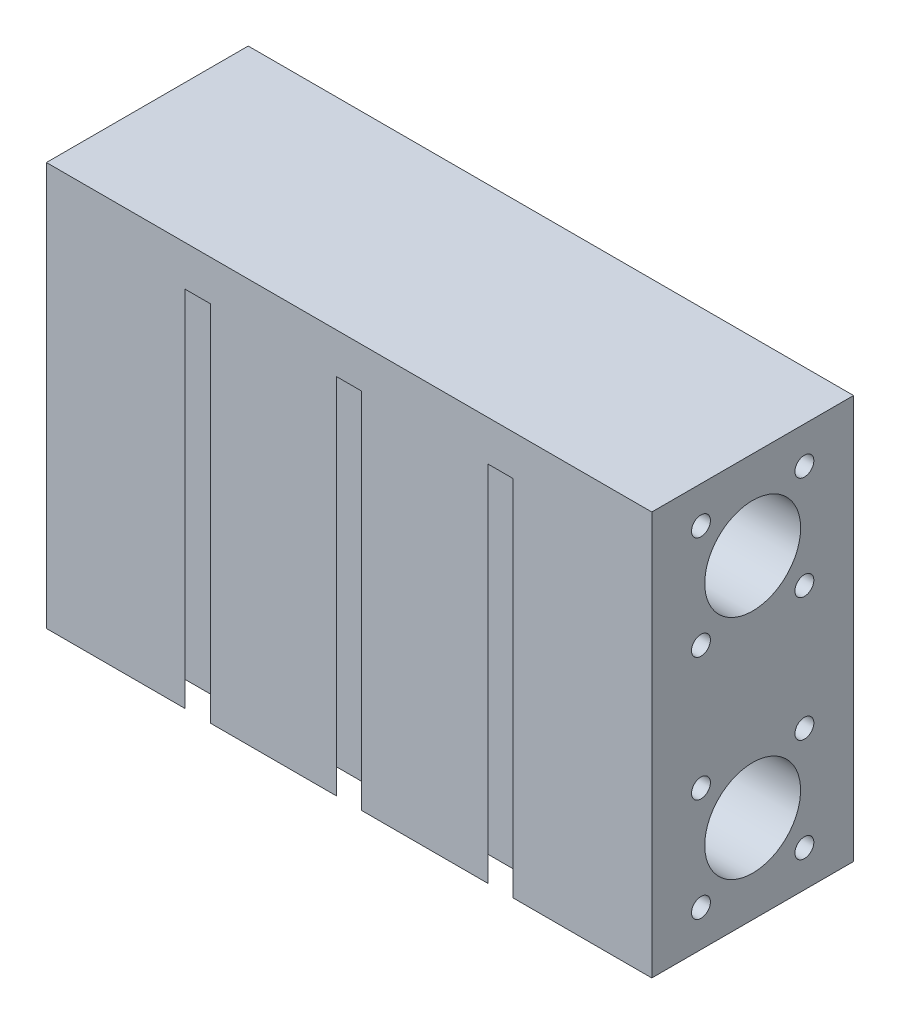
SolidWorks part; units mm, degrees
ref_plane "Front Plane" through (0, 0, 0) normal (0, 0, 1) x (1, 0, 0)
ref_plane "Top Plane" through (0, 0, 0) normal (0, 1, 0) x (1, 0, 0)
ref_plane "Right Plane" through (0, 0, 0) normal (1, 0, 0) x (0, 0, -1)
sketch "Sketch1" plane through (0, 0, 0) normal (0, 0, 1) x (1, 0, 0)
  line L1 (0, 0) -> (120, 0)
  line L2 (0, 0) -> (0, 80)
  line L3 (0, 80) -> (120, 80)
  line L4 (120, 0) -> (120, 80)
  dimension "D1" = 80
  dimension "D2" = 120
extrude "Boss-Extrude1" add sketch "Sketch1" along normal blind 40 contours L3 L4 L1 L2
sketch "Sketch2" plane through (0, 0, 0) normal (-1, 0, 0) x (0, 0, 1)
  line L0 (20, 80) -> (20, 0) construction
  line L1 (40, 80) -> (0, 80) construction
  line L2 (40, 0) -> (0, 0) construction
  line L3 (40, 40) -> (0, 40) construction
  line L4 (40, 0) -> (40, 80) construction
  line L5 (0, 0) -> (0, 80) construction
  line L6 (0, 62.5) -> (40, 62.5) construction
  line L7 (0, 17.5) -> (40, 17.5) construction
  circle A1 centre (30.25, 72.75) radius 1.85
  circle A2 centre (9.75, 72.75) radius 1.85
  circle A3 centre (30.25, 52.25) radius 1.85
  circle A4 centre (9.75, 52.25) radius 1.85
  circle A5 centre (9.75, 27.75) radius 1.85
  circle A6 centre (30.25, 27.75) radius 1.85
  circle A7 centre (30.25, 7.25) radius 1.85
  circle A9 centre (9.75, 7.25) radius 1.85
  dimension "D4" = 3.7
  dimension "D1" = 22.5
  dimension "D2" = 9.75
  dimension "D3" = 7.25
extrude "linear-bearing-screw-cuts" cut sketch "Sketch2" against normal blind 14
sketch "Sketch3" plane through (0, 0, 0) normal (-1, 0, 0) x (0, 0, 1)
  line L0 (20, 80) -> (20, 0) construction
  line L1 (40, 80) -> (0, 80) construction
  line L2 (40, 0) -> (0, 0) construction
  line L3 (0, 40) -> (40, 40) construction
  line L4 (0, 0) -> (0, 80) construction
  line L5 (40, 0) -> (40, 80) construction
  line L6 (0, 62.5) -> (40, 62.5) construction
  line L7 (0, 17.5) -> (40, 17.5) construction
  circle A0 centre (20, 62.5) radius 9.5
  circle A2 centre (20, 17.5) radius 9.5
  dimension "D2" = 19
  dimension "D1" = 45
extrude "linear-bearings-hole" cut sketch "Sketch3" against normal blind 55
sketch "Sketch4" plane through (120, 0, 0) normal (1, 0, 0) x (0, 0, -1)
  line L0 (-20, 80) -> (-20, 0) construction
  line L1 (-40, 80) -> (0, 80) construction
  line L2 (-40, 0) -> (0, 0) construction
  line L3 (-40, 40) -> (0, 40) construction
  line L4 (-40, 0) -> (-40, 80) construction
  line L5 (0, 0) -> (0, 80) construction
  line L6 (-40, 62.5) -> (0, 62.5) construction
  line L7 (-40, 17.5) -> (0, 17.5) construction
  circle A0 centre (-9.75, 72.75) radius 1.875
  circle A1 centre (-30.25, 72.75) radius 1.875
  circle A2 centre (-9.75, 52.25) radius 1.875
  circle A3 centre (-30.25, 52.25) radius 1.875
  circle A4 centre (-30.25, 27.75) radius 1.875
  circle A5 centre (-9.75, 27.75) radius 1.875
  circle A6 centre (-9.75, 7.25) radius 1.875
  circle A7 centre (-30.25, 7.25) radius 1.875
  dimension "D2" = 3.75
  dimension "D1" = 45
  dimension "D3" = 7.25
  dimension "D4" = 9.75
extrude "linear-bearing-screw-cuts2" cut sketch "Sketch4" against normal blind 14
sketch "Sketch5" plane through (120, 0, 0) normal (1, 0, 0) x (0, 0, -1)
  line L0 (-20, 80) -> (-20, 0) construction
  line L1 (-40, 80) -> (0, 80) construction
  line L2 (-40, 0) -> (0, 0) construction
  line L3 (0, 40) -> (-40, 40) construction
  line L4 (0, 0) -> (0, 80) construction
  line L5 (-40, 0) -> (-40, 80) construction
  line L6 (-40, 62.5) -> (0, 62.5) construction
  line L7 (-40, 17.5) -> (0, 17.5) construction
  circle A0 centre (-20, 62.5) radius 9.5
  circle A1 centre (-20, 17.5) radius 9.5
  dimension "D2" = 19
  dimension "D1" = 45
extrude "Cut-Extrude4" cut sketch "Sketch5" against normal blind 55
sketch "Sketch10" plane through (0, 0, 0) normal (0, -1, 0) x (1, 0, 0)
  line L0 (87.5, 40) -> (82.5, 35)
  line L1 (0, 40) -> (120, 40) construction
  line L2 (82.5, 35) -> (97.5, 35)
  line L3 (97.5, 35) -> (92.5, 40)
  line L4 (92.5, 40) -> (87.5, 40)
  line L5 (60, 40) -> (60, 0) construction
  line L6 (0, 0) -> (120, 0) construction
  line L7 (75, 40) -> (75, 0) construction
  line L8 (120, 40) -> (120, 0) construction
  line L9 (52.5, 35) -> (57.5, 40)
  line L10 (67.5, 35) -> (52.5, 35)
  line L11 (62.5, 40) -> (67.5, 35)
  line L12 (57.5, 40) -> (62.5, 40)
  line L13 (22.5, 35) -> (27.5, 40)
  line L14 (37.5, 35) -> (22.5, 35)
  line L15 (32.5, 40) -> (37.5, 35)
  line L16 (27.5, 40) -> (32.5, 40)
  point P12 (90, 40)
  dimension "D1" = 30
  dimension "D2" = 15
  dimension "D3" = 45
  dimension "D4" = 5
  dimension "D5" = 45
  dimension "D6" = 45
extrude "Cut-Extrude8" cut sketch "Sketch10" against normal blind 72
